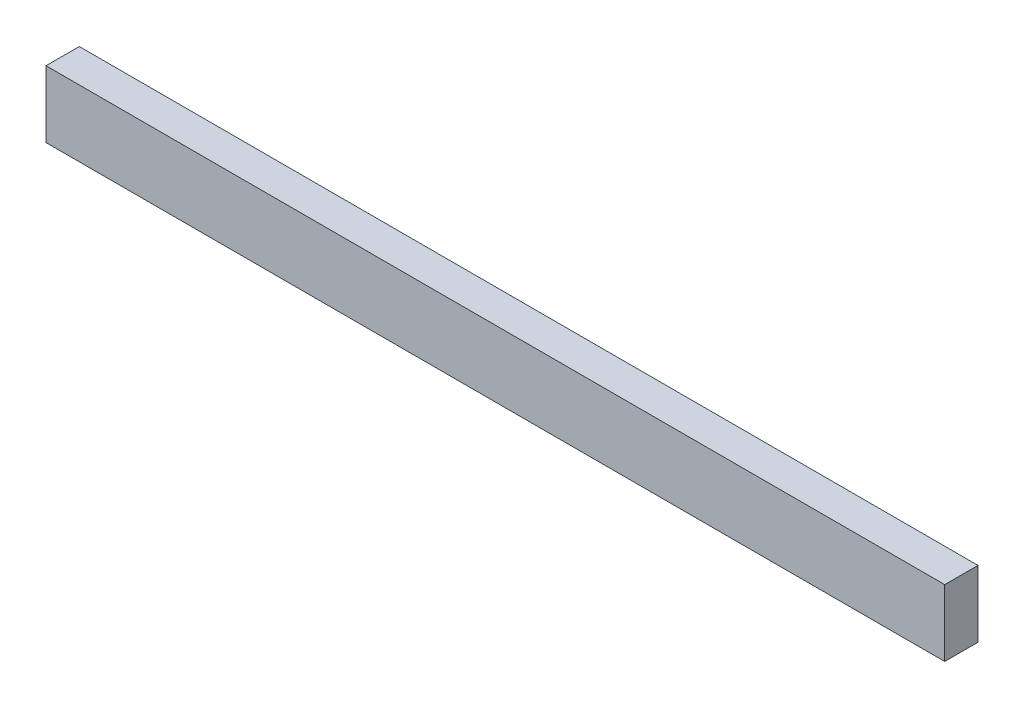
SolidWorks part; units mm, degrees
ref_plane "Front Plane" through (0, 0, 0) normal (0, 0, 1) x (1, 0, 0)
ref_plane "Top Plane" through (0, 0, 0) normal (0, 1, 0) x (1, 0, 0)
ref_plane "Right Plane" through (0, 0, 0) normal (1, 0, 0) x (0, 0, -1)
sketch "Sketch1" plane through (0, 0, 0) normal (0, 1, 0) x (1, 0, 0)
  line L1 (-110.7544, -32.9912) -> (159.2456, -32.9912)
  line L2 (-110.7544, -32.9912) -> (-110.7544, -42.9912)
  line L3 (-110.7544, -42.9912) -> (159.2456, -42.9912)
  line L4 (159.2456, -32.9912) -> (159.2456, -42.9912)
  dimension "D1" = 270
  dimension "D2" = 10
extrude "Boss-Extrude1" add sketch "Sketch1" along normal blind 20
